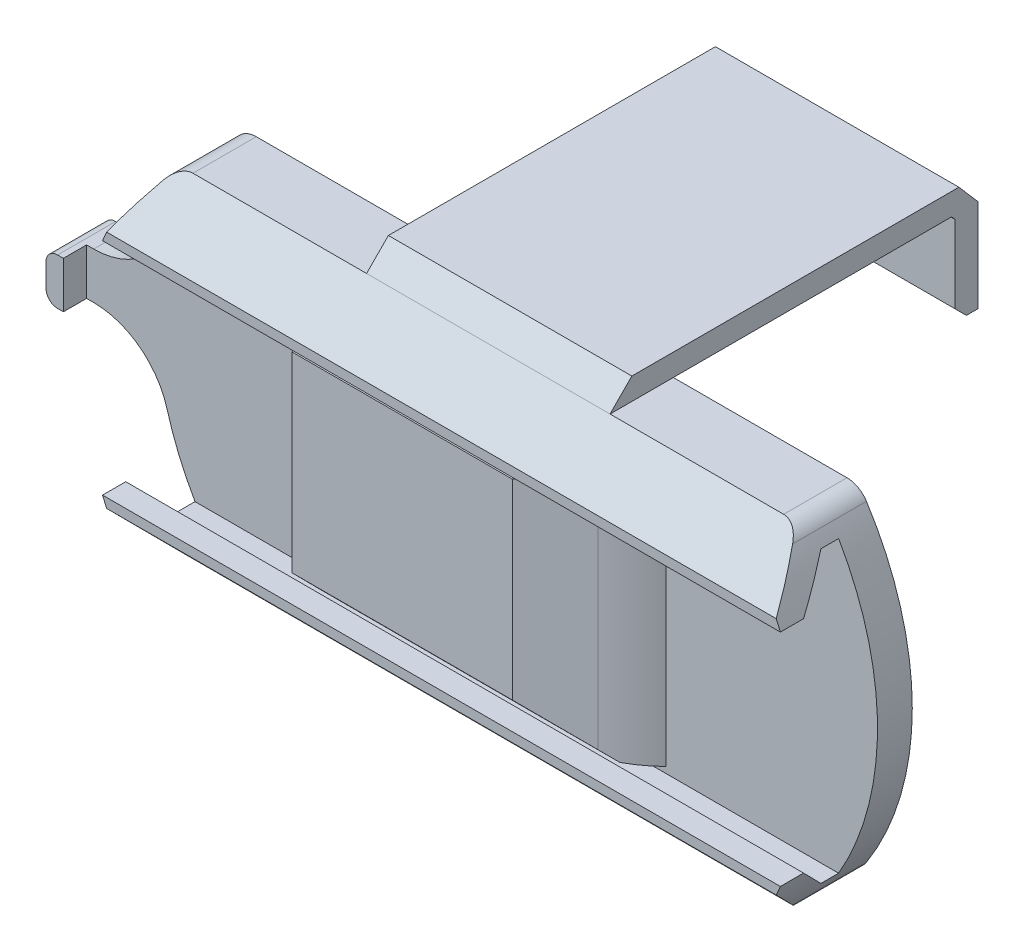
SolidWorks part; units mm, degrees
ref_plane "Front Plane" through (0, 0, 0) normal (0, 0, 1) x (1, 0, 0)
ref_plane "Top Plane" through (0, 0, 0) normal (0, 1, 0) x (1, 0, 0)
ref_plane "Right Plane" through (0, 0, 0) normal (1, 0, 0) x (0, 0, -1)
sketch "Sketch1" plane through (0, 0, 0) normal (0, 0, 1) x (1, 0, 0)
  line L1 (-26.54, -14.4) -> (26.54, -14.4)
  line L2 (-26.54, -14.4) -> (-26.54, 14.4) construction
  line L3 (-26.54, 14.4) -> (26.54, 14.4)
  line L4 (26.54, -14.4) -> (26.54, 14.4) construction
  line L5 (-26.54, -14.4) -> (26.54, 14.4) construction
  line L6 (-26.54, 14.4) -> (26.54, -14.4) construction
  line L8 (-2.7764, -7) -> (2.7764, -7)
  line L9 (-8, -1.7764) -> (-8, 1.7764)
  line L10 (-2.7764, 7) -> (2.7764, 7)
  line L11 (8, -1.7764) -> (8, 1.7764)
  line L12 (-8, -7) -> (8, 7) construction
  line L13 (-8, 7) -> (8, -7) construction
  arc A0 (-26.54, -14.4) -> (-26.54, 14.4) centre (-6.1379, 0) cw
  arc A1 (26.54, 14.4) -> (26.54, -14.4) centre (6.1379, 0) cw
  arc A2 (2.7764, 7) -> (8, 1.7764) centre (2.7764, 1.7764) cw
  arc A3 (2.7764, -7) -> (8, -1.7764) centre (2.7764, -1.7764) ccw
  arc A4 (-2.7764, -7) -> (-8, -1.7764) centre (-2.7764, -1.7764) cw
  arc A5 (-8, 1.7764) -> (-2.7764, 7) centre (-2.7764, 1.7764) cw
  point P0 (0, 0)
  point P8 (31.11, 0)
  point P9 (0, 0)
  point P10 (-31.11, 0)
  point P11 (0, 0)
  dimension "D3" = 62.22
  dimension "D4" = 14
  dimension "D1" = 28.8
  dimension "D2" = 53.08
  dimension "D5" = 16
extrude "Boss-Extrude1" add sketch "Sketch1" along normal blind 3
chamfer "Chamfer1" distance 2.5 angle 45 8 edges at (-6.47, -5.47, 3) (0, -7, 3) (6.47, -5.47, 3) (8, 0, 3) (6.47, 5.47, 3) (0, 7, 3) (-6.47, 5.47, 3) (-8, 0, 3)
sketch "Sketch2" plane through (0, 0, 0) normal (1, 0, 0) x (0, 0, -1)
  line L0 (-3, -9.5) -> (-3, -12.5) construction
  line L1 (-3, 14.4) -> (-3, -14.4) construction
  line L2 (-3, 9.5) -> (-3, 1.7764) construction
  line L3 (-3, 1.7764) -> (-3, -1.7764) construction
  line L4 (-3, -1.7764) -> (-3, -9.5) construction
  line L5 (-3, 9.5) -> (-3, 1.7764) construction
  line L6 (-3, 1.7764) -> (-3, -1.7764) construction
  line L7 (-3, -1.7764) -> (-3, -9.5) construction
  line L8 (-7.5, -9.5) -> (-4.527, -12.5)
  line L9 (-3, -12.5) -> (-4.527, -12.5)
  line L10 (-7.5, -12.5) -> (-7.5, -9.5) construction
  line L11 (-7.5, -9.5) -> (-9.5, -9.5)
  line L12 (-9.5, -9.5) -> (-9.5, -10.3231)
  line L13 (-5.4598, -14.4) -> (-3, -14.4)
  line L14 (-4.527, -12.5) -> (-7.5, -12.5) construction
  line L15 (-3, -14.4) -> (-3, -12.5)
  line L16 (-5.4598, -14.4) -> (-9.5, -10.3231)
  line L17 (-9.5, -10.3231) -> (-9.5, -14.4) construction
  line L18 (-9.5, -14.4) -> (-5.4598, -14.4) construction
  line L19 (-3, 0) -> (-15.1361, 0) construction
  line L20 (-5.4598, 14.4) -> (-9.5, 10.3231)
  line L21 (-9.5, 9.5) -> (-9.5, 10.3231)
  line L22 (-7.5, 9.5) -> (-9.5, 9.5)
  line L23 (-7.5, 9.5) -> (-4.527, 12.5)
  line L24 (-3, 12.5) -> (-4.527, 12.5)
  line L25 (-3, 14.4) -> (-3, 12.5)
  line L26 (-5.4598, 14.4) -> (-3, 14.4)
  dimension "D1" = 3
  dimension "D2" = 4.5
  dimension "D3" = 3
  dimension "D4" = 2
  dimension "D5" = 2
extrude "Boss-Extrude2" add sketch "Sketch2" along normal blind 33 and the other way blind 35
extrude "Cut-Extrude3" cut sketch "Sketch1<3>" along normal blind 33 flip side to cut
sketch "Sketch1<3>" plane through (0, 0, 0) normal (0, 0, 1) x (1, 0, 0) same geometry as "Sketch1"
sketch "Sketch3" plane through (0, 0, 0) normal (1, 0, 0) x (0, 0, -1)
  line L0 (-3.15, 11.5113) -> (-3.15, -10.8298)
  line L1 (-3.15, -10.8298) -> (-5.8302, -10.8298)
  line L2 (-5.8302, -10.8298) -> (-8.3853, -8.2515)
  line L3 (-8.3853, -8.2515) -> (-8.3853, 8.2515)
  line L4 (-8.3853, 8.2515) -> (-5.1548, 11.5113)
  line L5 (-5.1548, 11.5113) -> (-3.15, 11.5113)
  line L6 (-7.5, 9.5) -> (-4.527, 12.5) construction
  line L7 (-4.527, -12.5) -> (-7.5, -9.5) construction
  line L9 (-3, 12.5) -> (-3, -12.5) construction
  dimension "D1" = 0.25
  dimension "D2" = 0.25
  dimension "D3" = 0.15
extrude "Boss-Extrude3" add sketch "Sketch3" along normal blind 14 and the other way blind 14 separate body
chamfer "Chamfer3" distance 0.5 angle 45 2 edges at (0, 11.5113, 3.15) (0, -10.8298, 3.15)
sketch "Sketch4" plane through (0, 0, 0) normal (0, 0, -1) x (-1, 0, 0)
  line L0 (31.11, 0) -> (38.61, 0) construction
  line L1 (23.61, 2) -> (31.0298, 2) construction
  line L2 (23.61, 2) -> (23.61, -2) construction
  line L3 (36.497, -2) -> (37.61, -2)
  line L4 (38.61, 1) -> (38.61, -1)
  line L5 (23.61, 2) -> (38.61, -2) construction
  line L6 (23.61, -2) -> (38.61, 2) construction
  line L7 (36.497, 2) -> (37.61, 2)
  line L8 (31.0298, 2) -> (36.497, 2) construction
  line L9 (23.61, -2) -> (31.0298, -2) construction
  line L10 (31.0298, -2) -> (36.497, -2) construction
  line L11 (37.11, 2) -> (37.11, -2)
  arc A0 (26.54, -14.4) -> (26.54, 14.4) centre (6.1379, 0) ccw construction
  arc A1 (30.1698, 6.7876) -> (36.497, 2) centre (36.497, 8.5747) ccw
  arc A2 (30.1698, -6.7876) -> (30.1698, 6.7876) centre (6.1379, 0) ccw
  arc A3 (36.497, 2) -> (30.1698, 6.7876) centre (36.497, 8.5747) ccw construction
  arc A4 (30.1698, 6.7876) -> (26.54, 14.4) centre (6.1379, 0) ccw construction
  arc A5 (30.1698, -6.7876) -> (36.497, -2) centre (36.497, -8.5747) cw
  arc A6 (26.54, -14.4) -> (30.1698, -6.7876) centre (6.1379, 0) ccw construction
  arc A7 (37.61, -2) -> (38.61, -1) centre (37.61, -1) ccw
  arc A8 (37.61, 2) -> (38.61, 1) centre (37.61, 1) cw
  point P0 (31.11, 0)
  arc M15 (26.54, -14.4) -> (26.54, 14.4) centre (6.1379, 0) ccw
  dimension "D3" = 1
  dimension "D1" = 15
  dimension "D2" = 4
  dimension "D4" = 6
extrude "Boss-Extrude4" add sketch "Sketch4" against normal up to surface (3 mm away) contours A5 L3 L11 L7 A1 M15 | A8 L7 L11 L3 A7 L4 region at (-33.477, 0, 0) region at (-37.8194, 0, 0) up to face at (0, 0, 3)
extrude "Boss-Extrude5" add sketch "Sketch4<3>" against normal blind 2 from surface contours A8 L7 L11 L3 A7 L4 region at (-37.8194, 0, 0) starting at face at (0, 0, 3)
sketch "Sketch4<3>" plane through (0, 0, 0) normal (0, 0, -1) x (-1, 0, 0) same geometry as "Sketch4"
fillet "Fillet2" radius 2 4 edges at (-26.54, -14.4, 2.7299) (-26.54, 14.4, 2.7299) (26.54, 14.4, 2.7299) (26.54, -14.4, 2.7299)
sketch "Sketch5" plane through (0, 0, 0) normal (1, 0, 0) x (0, 0, -1)
  line L0 (0, 14.4) -> (24, 14.4)
  line L2 (24.6304, 16.298) -> (-3.5788, 16.298)
  line L3 (-3.5788, 16.298) -> (-5.4598, 14.4)
  line L4 (-5.4598, 14.4) -> (-6.372, 13.4796) construction
  line L5 (-6.372, 13.4796) -> (-9.5, 10.3231) construction
  line L6 (-5.4598, 14.4) -> (-6.372, 13.4796) construction
  line L7 (-6.372, 13.4796) -> (-9.5, 10.3231) construction
  line L8 (-5.4598, 14.4) -> (0, 14.4)
  line L9 (24.6304, 16.298) -> (26.278, 14.4)
  line L10 (26.278, 14.4) -> (26.278, 6.4)
  line L11 (26.278, 6.4) -> (25.278, 6.4)
  line L12 (24.278, 7.4) -> (24.278, 14.0797)
  line L13 (24.278, 14.0797) -> (24, 14.4)
  line L14 (25.278, 6.4) -> (24.278, 7.4)
  point P11 (24.278, 6.4)
  dimension "D1" = 24
  dimension "D2" = 2
  dimension "D3" = 8
  dimension "D4" = 2
extrude "Boss-Extrude6" add sketch "Sketch5" along normal up to vertex (10.5 mm away) and the other way up to vertex (10.5 mm away) separate body up to point (10.5, -1.7764, 3) other way up to point (-10.5, -1.7764, 3)
sketch "Sketch6" plane through (0, 14.4, 0) normal (0, 1, 0) x (1, 0, 0)
  line L0 (25.4759, 0) -> (-25.4759, 0) construction
  line L1 (-10.5, 0) -> (10.5, 0)
  line L2 (-10.5, 0) -> (-10.5, -1.8356)
  line L3 (-10.5, -1.8356) -> (10.5, -1.8356)
  line L4 (10.5, 0) -> (10.5, -1.8356)
  line L5 (-10.5, 24.6304) -> (-10.5, -3.5788) construction
  line L6 (10.5, 24.6304) -> (10.5, -3.5788) construction
  point P10 (0, 0)
  point P11 (0, 0)
extrude "Cut-Extrude4" cut sketch "Sketch6" against normal blind 4
sketch "Sketch7" plane through (0, 14.4, 0) normal (0, 1, 0) x (1, 0, 0)
  line L0 (10.5, 0) -> (-10.5, 0) construction
  line L1 (-10.3, 0) -> (10.3, 0)
  line L2 (-10.3, 0) -> (-10.3, -1.8356)
  line L3 (-10.3, -1.8356) -> (10.3, -1.8356)
  line L4 (10.3, 0) -> (10.3, -1.8356)
  line L5 (-10.5, -1.8356) -> (10.5, -1.8356) construction
  line L6 (-10.5, 0) -> (-10.5, -1.8356) construction
  line L7 (10.5, -1.8356) -> (10.5, 0) construction
  point P12 (0, 0)
  dimension "D1" = 0.2
  dimension "D2" = 0.2
extrude "Boss-Extrude8" add sketch "Sketch7" against normal blind 3.8
chamfer "Chamfer9" distance 0.5 angle 45 2 edges at (-10.3, 10.6, 0.9178) (10.3, 10.6, 0.9178)
chamfer "Chamfer10" distance 9 angle 20 1 edges at (14, 0, 8.3853) first distance on face at (0, 0, 8.3853)
chamfer "Chamfer11" distance 1 angle 45 1 edges at (14, 0.3408, 3.15)
chamfer "Chamfer12" distance 2 angle 45 1 edges at (-14, 0.3408, 3.15)
fillet "Fillet3" radius 10 1 edges at (14, 0.3408, 5.1096)
